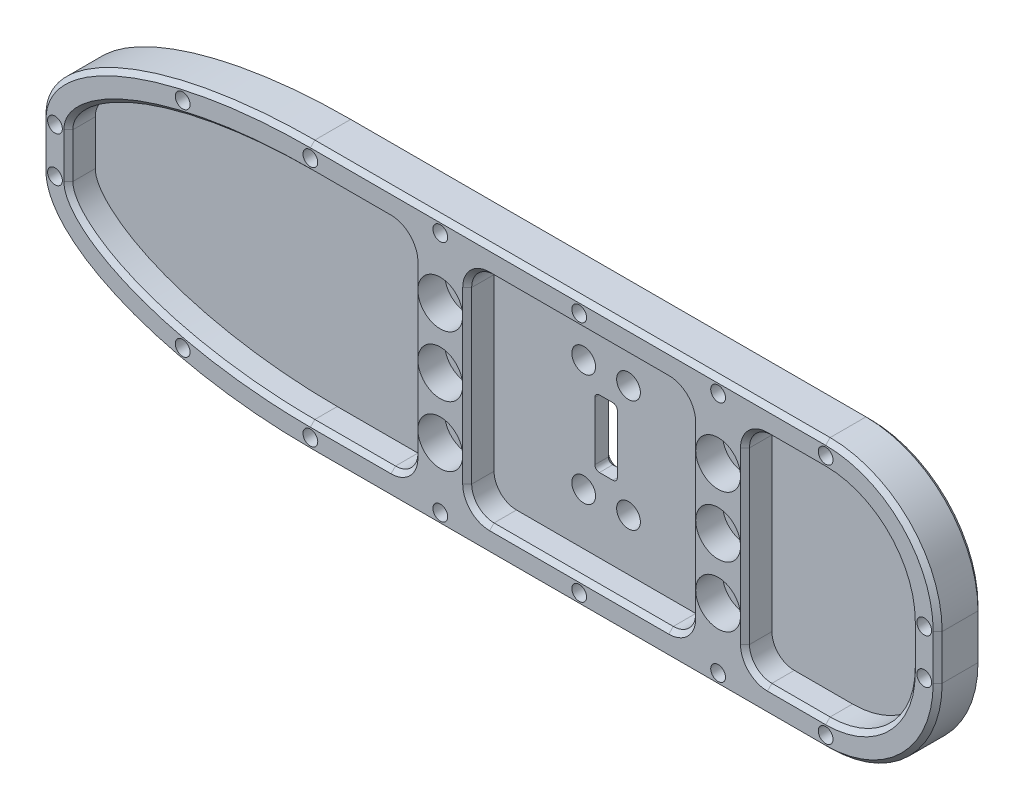
SolidWorks part; units mm, degrees
material "7075-T6 (SN)"
ref_plane "前视基准面" through (0, 0, 0) normal (0, 0, 1) x (1, 0, 0)
ref_plane "上视基准面" through (0, 0, 0) normal (0, 1, 0) x (1, 0, 0)
ref_plane "右视基准面" through (0, 0, 0) normal (1, 0, 0) x (0, 0, -1)
sketch "草图1" plane through (0, 0, 0) normal (0, 0, 1) x (1, 0, 0)
  line L0 (-20, 6.5) -> (-20, -6.5) construction
  line L1 (-19.4142, 6.5) -> (-20.5858, 6.5) construction
  line L2 (-20.5858, -6.5) -> (-19.4142, -6.5) construction
  line L3 (-20, 30) -> (-20, -30) construction
  line L4 (-20, 0) -> (60, 0) construction
  line L5 (-20, 0) -> (-140, 0) construction
  line L6 (-140, 0) -> (-140, -30) construction
  line L7 (60, 0) -> (60, 30) construction
  line L8 (-45, -14.5) -> (-45, -16.5) construction
  line L9 (-140, -30) -> (60, -30)
  line L10 (-140, -30) -> (-140, 30)
  line L11 (-140, 30) -> (60, 30)
  line L12 (60, -30) -> (60, 30)
  line L13 (-45, -16.5) -> (-57, -16.5) construction
  line L14 (-47, -16.5) -> (-55, -16.5) construction
  line L15 (17, -14.5) -> (17, -16.5) construction
  line L16 (15, -16.5) -> (17, -14.5) construction
  line L17 (17, 14.5) -> (17, -14.5) construction
  line L18 (17, -16.5) -> (15, -16.5) construction
  line L20 (-45, -16.5) -> (-57, -16.5)
  line L21 (-45, -16.5) -> (-45, 16.5)
  line L22 (-45, 16.5) -> (-57, 16.5)
  line L23 (-57, -16.5) -> (-57, 16.5)
  line L24 (17, -16.5) -> (5, -16.5)
  line L25 (17, -16.5) -> (17, 16.5)
  line L26 (17, 16.5) -> (5, 16.5)
  line L27 (5, -16.5) -> (5, 16.5)
  line L28 (-22.5, 7.5) -> (-17.5, 7.5)
  line L29 (-22.5, 7.5) -> (-22.5, -7.5)
  line L30 (-22.5, -7.5) -> (-17.5, -7.5)
  line L31 (-17.5, 7.5) -> (-17.5, -7.5)
  line L32 (-22.5, 7.5) -> (-17.5, -7.5) construction
  line L33 (-22.5, -7.5) -> (-17.5, 7.5) construction
  point P10 (-20, 0)
extrude "凸台-拉伸1" add sketch "草图1" along normal blind 10
fillet "圆角1" radius 1 12 edges at (5, 16.5, 5) (5, -16.5, 5) (17, -16.5, 5) (17, 16.5, 5) (-22.5, 7.5, 5) (-22.5, -7.5, 5) (-17.5, -7.5, 5) (-17.5, 7.5, 5) (-57, -16.5, 5) (-45, -16.5, 5) (-45, 16.5, 5) (-57, 16.5, 5)
fillet "圆角2" radius 25 2 edges at (60, -30, 5) (60, 30, 5)
fillet "圆角3" radius 60 2 edges at (-140, -30, 5) (-140, 30, 5)
sketch "草图2" plane through (0, 0, 2) normal (0, 0, 1) x (1, 0, 0)
  line L0 (6, -16.5) -> (16, -16.5) construction
  line L1 (17, -15.5) -> (17, 15.5) construction
  line L2 (16, 16.5) -> (6, 16.5) construction
  line L3 (5, 15.5) -> (5, -15.5) construction
  line L4 (-45, -15.5) -> (-45, 15.5) construction
  line L5 (-56, -16.5) -> (-46, -16.5) construction
  line L6 (-57, 15.5) -> (-57, -15.5) construction
  line L7 (-46, 16.5) -> (-56, 16.5) construction
  line L8 (6, -16.5) -> (16, -16.5)
  line L9 (17, -15.5) -> (17, 15.5)
  line L10 (16, 16.5) -> (6, 16.5)
  line L11 (5, 15.5) -> (5, -15.5)
  line L12 (-45, -15.5) -> (-45, 15.5)
  line L13 (-56, -16.5) -> (-46, -16.5)
  line L14 (-57, 15.5) -> (-57, -15.5)
  line L15 (-46, 16.5) -> (-56, 16.5)
  arc A0 (16, -16.5) -> (17, -15.5) centre (16, -15.5) ccw construction
  arc A1 (17, 15.5) -> (16, 16.5) centre (16, 15.5) ccw construction
  arc A2 (6, 16.5) -> (5, 15.5) centre (6, 15.5) ccw construction
  arc A3 (-46, -16.5) -> (-45, -15.5) centre (-46, -15.5) ccw construction
  arc A4 (-57, -15.5) -> (-56, -16.5) centre (-56, -15.5) ccw construction
  arc A5 (-56, 16.5) -> (-57, 15.5) centre (-56, 15.5) ccw construction
  arc A6 (-45, 15.5) -> (-46, 16.5) centre (-46, 15.5) ccw construction
  arc A7 (16, -16.5) -> (17, -15.5) centre (16, -15.5) ccw
  arc A8 (17, 15.5) -> (16, 16.5) centre (16, 15.5) ccw
  arc A9 (6, 16.5) -> (5, 15.5) centre (6, 15.5) ccw
  arc A10 (-46, -16.5) -> (-45, -15.5) centre (-46, -15.5) ccw
  arc A11 (-57, -15.5) -> (-56, -16.5) centre (-56, -15.5) ccw
  arc A12 (-56, 16.5) -> (-57, 15.5) centre (-56, 15.5) ccw
  arc A13 (-45, 15.5) -> (-46, 16.5) centre (-46, 15.5) ccw
  arc A14 (5, -15.5) -> (6, -16.5) centre (6, -15.5) ccw construction
  arc A15 (5, -15.5) -> (6, -16.5) centre (6, -15.5) ccw
extrude "凸台-拉伸2" add sketch "草图2" along normal up to surface (8 mm away) up to face at (11, 0, 10)
sketch "草图3" plane through (0, 0, 10) normal (0, 0, 1) x (1, 0, 0)
  line L0 (-45, 24) -> (-45, -24)
  line L1 (-57, 24) -> (-57, -24)
  line L2 (17, 24) -> (17, -24)
  line L3 (5, 24) -> (5, -24)
  line L4 (-57, 24) -> (-80, 24)
  line L5 (-45, -24) -> (5, -24)
  line L6 (17, -24) -> (35, -24)
  line L7 (5, 24) -> (-45, 24)
  line L8 (11, 13.5) -> (11, -13.5) construction
  line L9 (5, 0) -> (17, 0) construction
  line L10 (-51, -13.5) -> (-51, 13.5) construction
  line L11 (-45, 0) -> (-57, 0) construction
  line L12 (-134, 5) -> (-134, -5)
  line L13 (-80, -24) -> (35, -24)
  line L14 (54, -5) -> (54, 5)
  line L15 (35, 24) -> (-80, 24)
  line L16 (-134, 5) -> (-134, -5)
  line L17 (-80, -24) -> (-57, -24)
  line L18 (54, -5) -> (54, 5)
  line L19 (35, 24) -> (17, 24)
  line L20 (11, 13.5) -> (11, -13.5) construction
  line L21 (5, 0) -> (17, 0) construction
  line L22 (-51, -13.5) -> (-51, 13.5) construction
  line L23 (-45, 0) -> (-57, 0) construction
  arc A6 (35, -24) -> (54, -5) centre (35, -5) ccw
  arc A7 (54, 5) -> (35, 24) centre (35, 5) ccw
  arc A8 (35, -24) -> (54, -5) centre (35, -5) ccw
  arc A9 (54, 5) -> (35, 24) centre (35, 5) ccw
  spline S6 degree 3 poles (4756.0393, 1030.7106) (198.0526, 126.1715) (-140.7078, 27.1267) (-133.8393, -6.2556) (-133.7451, -6.5606) (-133.3923, -7.4528) (-133.0755, -7.9996) (-132.5322, -8.7799) (-132.3384, -9.0338) (-131.9356, -9.5251) (-131.7265, -9.7624) (-131.0797, -10.4534) (-130.623, -10.8863) (-129.6715, -11.711) (-129.1766, -12.1027) (-128.1565, -12.8532) (-127.6333, -13.2105) (-126.0438, -14.2321) (-124.9533, -14.8516) (-122.7261, -15.9976) (-121.5891, -16.5239) (-119.278, -17.5022) (-118.1026, -17.9545) (-114.538, -19.2166) (-112.1371, -19.9264) (-107.2998, -21.1552) (-104.8628, -21.6707) (-99.9581, -22.5373) (-97.4905, -22.8885) (-92.5289, -23.4494) (-90.0346, -23.6574) (236.6094, -41.6102) (593.0658, 1124.1985) (755.533, -4814.3595) knots -1.654516 -1.654516 -1.654516 -1.654516 0.015625 0.015625 0.03125 0.03125 0.0625 0.0625 0.078125 0.078125 0.09375 0.09375 0.125 0.125 0.15625 0.15625 0.1875 0.1875 0.25 0.25 0.3125 0.3125 0.375 0.375 0.5 0.5 0.625 0.625 0.75 0.75 0.875 0.875 17.035108 17.035108 17.035108 17.035108 only from (-134, -5) to (-80, -24)
  spline S7 degree 3 poles (501.663, 4795.8892) (785.7927, -1434.1881) (265.311, 63.8012) (-97.4581, 22.8929) (-99.932, 22.5416) (-103.6298, 21.8888) (-104.8602, 21.65) (-107.3161, 21.1259) (-108.5407, 20.8406) (-112.187, 19.9126) (-114.588, 19.2002) (-118.1299, 17.9441) (-119.3003, 17.4933) (-121.6158, 16.512) (-122.7595, 15.9817) (-124.4353, 15.1174) (-124.9878, 14.8176) (-126.0788, 14.1912) (-126.6182, 13.864) (-128.2033, 12.8419) (-129.2168, 12.1066) (-130.6342, 10.8757) (-131.0893, 10.4438) (-131.9519, 9.5207) (-132.3575, 9.0316) (-133.078, 7.9954) (-133.3979, 7.4401) (-133.7446, 6.5616) (-133.8382, 6.2604) (-141.744, -32.1036) (315.149, -131.378) (4388.3188, 2104.2864) knots -17.899786 -17.899786 -17.899786 -17.899786 0.25 0.25 0.375 0.375 0.4375 0.4375 0.5 0.5 0.625 0.625 0.6875 0.6875 0.75 0.75 0.78125 0.78125 0.8125 0.8125 0.875 0.875 0.90625 0.90625 0.9375 0.9375 0.96875 0.96875 0.984375 0.984375 2.888005 2.888005 2.888005 2.888005 only from (-80, 24) to (-134, 5)
  spline S8 degree 3 poles (-134, -5) (-134, -5.3216) (-133.9666, -5.6368) (-133.8393, -6.2556) (-133.7451, -6.5606) (-133.3923, -7.4528) (-133.0755, -7.9996) (-132.5322, -8.7799) (-132.3384, -9.0338) (-131.9356, -9.5251) (-131.7265, -9.7624) (-131.0797, -10.4534) (-130.623, -10.8863) (-129.6715, -11.711) (-129.1766, -12.1027) (-128.1565, -12.8532) (-127.6333, -13.2105) (-126.0438, -14.2321) (-124.9533, -14.8516) (-122.7261, -15.9976) (-121.5891, -16.5239) (-119.278, -17.5022) (-118.1026, -17.9545) (-114.538, -19.2166) (-112.1371, -19.9264) (-107.2998, -21.1552) (-104.8628, -21.6707) (-99.9581, -22.5373) (-97.4905, -22.8885) (-92.5289, -23.4494) (-90.0346, -23.6574) (-85.0202, -23.933) (-82.511, -24) (-80, -24) knots 0 0 0 0 0.015625 0.015625 0.03125 0.03125 0.0625 0.0625 0.078125 0.078125 0.09375 0.09375 0.125 0.125 0.15625 0.15625 0.1875 0.1875 0.25 0.25 0.3125 0.3125 0.375 0.375 0.5 0.5 0.625 0.625 0.75 0.75 0.875 0.875 1 1 1 1
  spline S9 degree 3 poles (-80, 24) (-85.021, 24) (-90.0141, 23.7323) (-97.4581, 22.8929) (-99.932, 22.5416) (-103.6298, 21.8888) (-104.8602, 21.65) (-107.3161, 21.1259) (-108.5407, 20.8406) (-112.187, 19.9126) (-114.588, 19.2002) (-118.1299, 17.9441) (-119.3003, 17.4933) (-121.6158, 16.512) (-122.7595, 15.9817) (-124.4353, 15.1174) (-124.9878, 14.8176) (-126.0788, 14.1912) (-126.6182, 13.864) (-128.2033, 12.8419) (-129.2168, 12.1066) (-130.6342, 10.8757) (-131.0893, 10.4438) (-131.9519, 9.5207) (-132.3575, 9.0316) (-133.078, 7.9954) (-133.3979, 7.4401) (-133.7446, 6.5616) (-133.8382, 6.2604) (-133.9669, 5.6357) (-134, 5.3193) (-134, 5) knots 0 0 0 0 0.25 0.25 0.375 0.375 0.4375 0.4375 0.5 0.5 0.625 0.625 0.6875 0.6875 0.75 0.75 0.78125 0.78125 0.8125 0.8125 0.875 0.875 0.90625 0.90625 0.9375 0.9375 0.96875 0.96875 0.984375 0.984375 1 1 1 1
  point P3 (45.7284, 30.0076)
  point P9 (-51, 0)
  point P13 (-45, 0)
  point P14 (11, 0)
  point P18 (-57, 0)
  point P21 (17, 0)
  point P24 (5, 0)
  dimension "D1" = 6
extrude "切除-拉伸1" cut sketch "草图3" against normal blind 6
hole_wizard "打孔尺寸(%根据)内六角圆柱头螺钉的类型1" positions "草图4" profile "草图5" counterbore size "M5" standard "GB" end condition through all
sketch "草图4" plane through (0, 0, 10) normal (0, 0, 1) x (1, 0, 0)
  point P0 (11, 13.5)
  point P3 (11, 0)
  point P6 (11, -13.5)
  point P9 (-51, -13.5)
  point P12 (-51, 0)
  point P15 (-51, 13.5)
sketch "草图5" plane through (11, 13.5, 10) normal (1, 0, 0) x (0, -1, 0)
  line L0 (0, 0) -> (0, 10.2125)
  line L1 (0, 10.2125) -> (2.65, 10.2125)
  line L3 (2.65, 10.2125) -> (2.65, 6)
  line L4 (2.65, 6) -> (5, 6)
  line L5 (5, 6) -> (5, 0)
  line L7 (5, 0) -> (0, 0)
  line L11 (0, -6.35) -> (0, 107.95) construction
  dimension "通孔孔直径" = 5.3
  dimension "通孔孔深度" = 10.2125
  dimension "柱形沉头孔直径" = 10
  dimension "柱形沉头孔深度" = 6
fillet "圆角4" radius 5 8 edges at (-57, 24, 7) (-57, -24, 7) (-45, -24, 7) (-45, 24, 7) (5, -24, 7) (5, 24, 7) (17, 24, 7) (17, -24, 7)
sketch "草图6" plane through (0, 0, 10) normal (0, 0, 1) x (1, 0, 0)
  line L4 (-80, 27) -> (-80, -27) construction
  line L5 (-137, 0) -> (-80, 0) construction
  line L6 (-108.5, 23.9242) -> (-108.5, -23.9242) construction
  line L7 (-51, 27) -> (-51, -27) construction
  line L8 (-137, 5) -> (-137, -5)
  line L9 (-80, -27) -> (35, -27)
  line L10 (57, -5) -> (57, 5)
  line L11 (35, 27) -> (-80, 27)
  line L12 (-137, 5) -> (-137, -5)
  line L13 (-80, -27) -> (35, -27)
  line L14 (57, -5) -> (57, 5)
  line L15 (35, 27) -> (-80, 27)
  line L16 (11, 27) -> (11, -27) construction
  line L17 (-51, 0) -> (11, 0) construction
  line L18 (-20, 27) -> (-20, -27) construction
  circle A2 centre (-51, 0) radius 2.65 construction
  circle A3 centre (11, 0) radius 2.65 construction
  arc A4 (35, -27) -> (57, -5) centre (35, -5) ccw
  arc A5 (57, 5) -> (35, 27) centre (35, 5) ccw
  arc A6 (35, -27) -> (57, -5) centre (35, -5) ccw
  arc A7 (57, 5) -> (35, 27) centre (35, 5) ccw
  spline S4 degree 3 poles (2782.2306, 680.8949) (128.842, 125.5863) (-147.0775, 31.5162) (-136.6428, -7.3449) (-136.5338, -7.6695) (-136.279, -8.3079) (-136.1352, -8.6171) (-135.6629, -9.52) (-135.2941, -10.0892) (-134.6819, -10.9071) (-134.4672, -11.1745) (-134.0239, -11.6939) (-133.7954, -11.9458) (-132.6233, -13.1713) (-131.5927, -14.0453) (-129.9577, -15.2544) (-129.3959, -15.641) (-128.2549, -16.3796) (-127.6765, -16.7317) (-125.9211, -17.7438) (-124.7238, -18.3596) (-122.287, -19.4992) (-121.0475, -20.0229) (-118.5341, -20.9954) (-117.2602, -21.4441) (-114.6838, -22.2791) (-113.3859, -22.664) (-109.4766, -23.7321) (-106.8451, -24.3282) (-102.8661, -25.0782) (-101.5344, -25.3041) (-98.8614, -25.7114) (-97.5193, -25.8929) (205.734, -62.1468) (578.3357, 968.5126) (632.357, -2808.3144) knots -1.805421 -1.805421 -1.805421 -1.805421 0.03125 0.03125 0.046875 0.046875 0.0625 0.0625 0.09375 0.09375 0.109375 0.109375 0.125 0.125 0.1875 0.1875 0.21875 0.21875 0.25 0.25 0.3125 0.3125 0.375 0.375 0.4375 0.4375 0.5 0.5 0.625 0.625 0.6875 0.6875 0.75 0.75 14.803914 14.803914 14.803914 14.803914 only from (-137, -5) to (-80, -27)
  spline S5 degree 3 poles (608.4548, 2791.2011) (646.334, -1069.663) (220.7438, 63.8682) (-98.8246, 25.7375) (-101.4933, 25.336) (-105.4826, 24.5856) (-106.808, 24.3109) (-109.4368, 23.7111) (-110.742, 23.3856) (-114.6276, 22.3262) (-117.1797, 21.514) (-120.9271, 20.0719) (-122.1626, 19.5534) (-124.5992, 18.4214) (-125.8005, 17.8082) (-128.1585, 16.4583) (-129.3213, 15.7193) (-130.9745, 14.5051) (-131.5114, 14.0819) (-132.5503, 13.1895) (-133.0534, 12.7189) (-133.9994, 11.7349) (-134.4441, 11.2204) (-135.2628, 10.1351) (-135.637, 9.5644) (-136.2823, 8.3414) (-136.5426, 7.7082) (-136.8128, 6.7166) (-136.8829, 6.3774) (-145.3112, -55.3716) (594.7178, -178.7084) (2829.5936, -425.7435) knots -14.55071 -14.55071 -14.55071 -14.55071 0.25 0.25 0.375 0.375 0.4375 0.4375 0.5 0.5 0.625 0.625 0.6875 0.6875 0.75 0.75 0.8125 0.8125 0.84375 0.84375 0.875 0.875 0.90625 0.90625 0.9375 0.9375 0.96875 0.96875 0.984375 0.984375 3.782552 3.782552 3.782552 3.782552 only from (-80, 27) to (-137, 5)
  spline S6 degree 3 poles (-137, -5) (-137, -5.6898) (-136.9068, -6.3615) (-136.6428, -7.3449) (-136.5338, -7.6695) (-136.279, -8.3079) (-136.1352, -8.6171) (-135.6629, -9.52) (-135.2941, -10.0892) (-134.6819, -10.9071) (-134.4672, -11.1745) (-134.0239, -11.6939) (-133.7954, -11.9458) (-132.6233, -13.1713) (-131.5927, -14.0453) (-129.9577, -15.2544) (-129.3959, -15.641) (-128.2549, -16.3796) (-127.6765, -16.7317) (-125.9211, -17.7438) (-124.7238, -18.3596) (-122.287, -19.4992) (-121.0475, -20.0229) (-118.5341, -20.9954) (-117.2602, -21.4441) (-114.6838, -22.2791) (-113.3859, -22.664) (-109.4766, -23.7321) (-106.8451, -24.3282) (-102.8661, -25.0782) (-101.5344, -25.3041) (-98.8614, -25.7114) (-97.5193, -25.8929) (-90.8061, -26.6955) (-85.4131, -27) (-80, -27) knots 0 0 0 0 0.03125 0.03125 0.046875 0.046875 0.0625 0.0625 0.09375 0.09375 0.109375 0.109375 0.125 0.125 0.1875 0.1875 0.21875 0.21875 0.25 0.25 0.3125 0.3125 0.375 0.375 0.4375 0.4375 0.5 0.5 0.625 0.625 0.6875 0.6875 0.75 0.75 1 1 1 1
  spline S7 degree 3 poles (-80, 27) (-85.4119, 27) (-90.7956, 26.6955) (-98.8246, 25.7375) (-101.4933, 25.336) (-105.4826, 24.5856) (-106.808, 24.3109) (-109.4368, 23.7111) (-110.742, 23.3856) (-114.6276, 22.3262) (-117.1797, 21.514) (-120.9271, 20.0719) (-122.1626, 19.5534) (-124.5992, 18.4214) (-125.8005, 17.8082) (-128.1585, 16.4583) (-129.3213, 15.7193) (-130.9745, 14.5051) (-131.5114, 14.0819) (-132.5503, 13.1895) (-133.0534, 12.7189) (-133.9994, 11.7349) (-134.4441, 11.2204) (-135.2628, 10.1351) (-135.637, 9.5644) (-136.2823, 8.3414) (-136.5426, 7.7082) (-136.8128, 6.7166) (-136.8829, 6.3774) (-136.9765, 5.6916) (-137, 5.3468) (-137, 5) knots 0 0 0 0 0.25 0.25 0.375 0.375 0.4375 0.4375 0.5 0.5 0.625 0.625 0.6875 0.6875 0.75 0.75 0.8125 0.8125 0.84375 0.84375 0.875 0.875 0.90625 0.90625 0.9375 0.9375 0.96875 0.96875 0.984375 0.984375 1 1 1 1
  point P5 (-108.5, 0)
  point P9 (-51, 0)
  point P21 (11, 0)
  point P31 (-20, 0)
  dimension "D1" = 3
hole_wizard "M4 螺纹孔1" positions "草图8" profile "草图9" tap size "M4" standard "GB" end condition through all
sketch "草图8" plane through (0, 0, 10) normal (0, 0, 1) x (1, 0, 0)
  point P0 (-137, 5)
  point P3 (-137, -5)
  point P6 (-108.5, -23.9242)
  point P9 (-108.5, 23.9242)
  point P12 (-80, 27)
  point P15 (-80, -27)
  point P18 (-51, -27)
  point P21 (-51, 27)
  point P24 (-20, 27)
  point P27 (-20, -27)
  point P30 (11, -27)
  point P33 (11, 27)
  point P36 (35, 27)
  point P39 (57, 5)
  point P42 (57, -5)
  point P45 (35, -27)
sketch "草图9" plane through (-137, 5, 10) normal (1, 0, 0) x (0, -1, 0)
  line L0 (0, 0) -> (0, 10.2125)
  line L1 (0, 10.2125) -> (1.65, 10.2125)
  line L2 (1.65, 10.2125) -> (1.65, 0)
  line L5 (1.65, 0) -> (0, 0)
  line L11 (0, -6.35) -> (0, 107.95) construction
  dimension "通孔螺纹孔钻头直径" = 3.3
  dimension "通孔螺纹孔钻头深度" = 10.2125
cosmetic thread "孔螺蚊线1" parameters "D2"=4
cosmetic thread "孔螺蚊线2" parameters "D2"=4
cosmetic thread "孔螺蚊线3" parameters "D2"=4
cosmetic thread "孔螺蚊线4" parameters "D2"=4
cosmetic thread "孔螺蚊线5" parameters "D2"=4
cosmetic thread "孔螺蚊线6" parameters "D2"=4
cosmetic thread "孔螺蚊线7" parameters "D2"=4
cosmetic thread "孔螺蚊线8" parameters "D2"=4
cosmetic thread "孔螺蚊线9" parameters "D2"=4
cosmetic thread "孔螺蚊线10" parameters "D2"=4
cosmetic thread "孔螺蚊线11" parameters "D2"=4
cosmetic thread "孔螺蚊线12" parameters "D2"=4
cosmetic thread "孔螺蚊线13" parameters "D2"=4
cosmetic thread "孔螺蚊线14" parameters "D2"=4
cosmetic thread "孔螺蚊线15" parameters "D2"=4
cosmetic thread "孔螺蚊线16" parameters "D2"=4
chamfer "倒角1" distance 1 angle 45 16 edges at (11, 16.5, 0) (5.2929, 16.2071, 0) (16.7071, 16.2071, 0) (5, 0, 0) (17, 0, 0) (5.2929, -16.2071, 0) (16.7071, -16.2071, 0) (11, -16.5, 0) (-51, 16.5, 0) (-56.7071, 16.2071, 0) (-45.2929, 16.2071, 0) (-57, 0, 0) (-45, 0, 0) (-56.7071, -16.2071, 0) (-45.2929, -16.2071, 0) (-51, -16.5, 0)
chamfer "倒角2" distance 1 angle 45 8 edges at (-22.5, 0, 0) (-22.2071, -7.2071, 0) (-22.2071, 7.2071, 0) (-20, -7.5, 0) (-20, 7.5, 0) (-17.7929, -7.2071, 0) (-17.7929, 7.2071, 0) (-17.5, 0, 0)
chamfer "倒角3" distance 1 angle 45 40 edges at (52.6777, -22.6777, 0) (60, 0, 0) (52.6777, 22.6777, 0) (52.6777, -22.6777, 10) (60, 0, 10) (52.6777, 22.6777, 10) (28.5, -24, 10) (48.435, -18.435, 10) (18.4645, -22.5355, 10) (54, 0, 10) (17, 0, 10) (48.435, 18.435, 10) (18.4645, 22.5355, 10) (28.5, 24, 10) (-20, -24, 10) (3.5355, -22.5355, 10) (-43.5355, -22.5355, 10) (5, 0, 10) (-45, 0, 10) (3.5355, 22.5355, 10) (-43.5355, 22.5355, 10) (-20, 24, 10) (-58.4645, -22.5355, 10) (-57, 0, 10) (-58.4645, 22.5355, 10)
sketch "草图10" plane through (0, 0, 0) normal (0, 0, -1) x (-1, 0, 0)
  line L8 (62, 19) -> (62, -19)
  line L9 (80, 19) -> (62, 19)
  line L10 (129, -4.9576) -> (129, 4.9581)
  line L11 (62, -19) -> (80, -19)
  line L12 (62, 19) -> (62, -19)
  line L13 (80, 19) -> (62, 19)
  line L14 (129, -4.9576) -> (129, 4.9581)
  line L15 (62, -19) -> (80, -19)
  spline S4 degree 3 poles (-3735.683, -1014.249) (124.4511, -12.6691) (131.4253, 0.0295) (128.8891, 5.2126) (128.8559, 5.2737) (128.7515, 5.4537) (128.6757, 5.5693) (128.4375, 5.9085) (128.2634, 6.1249) (127.7168, 6.7477) (127.3222, 7.1281) (126.4973, 7.8476) (126.0669, 8.1866) (125.1791, 8.8335) (124.7213, 9.1416) (123.3336, 10.0224) (122.3834, 10.5552) (120.4468, 11.5423) (119.4602, 11.9961) (117.4586, 12.8422) (116.4434, 13.2342) (114.3899, 13.9678) (113.3501, 14.3105) (110.216, 15.2686) (108.1068, 15.8171) (103.8565, 16.7692) (101.7151, 17.1714) (97.4049, 17.8511) (95.2354, 18.1285) (-211.1327, 49.2518) (-590.0843, -1053.6287) (-573.8669, 3836.9878) knots -0.317011 -0.317011 -0.317011 -0.317011 0.003906 0.003906 0.007812 0.007812 0.015625 0.015625 0.03125 0.03125 0.0625 0.0625 0.09375 0.09375 0.125 0.125 0.1875 0.1875 0.25 0.25 0.3125 0.3125 0.375 0.375 0.5 0.5 0.625 0.625 0.75 0.75 18.271622 18.271622 18.271622 18.271622 only from (129, 4.9581) to (80, 19)
  spline S5 degree 3 poles (-505.3503, -3825.5156) (-668.7083, 1167.0576) (-226.9123, -50.8123) (95.2138, -18.131) (97.3724, -17.8555) (100.6011, -17.3474) (101.6758, -17.1621) (103.8218, -16.7569) (104.8941, -16.5365) (108.0931, -15.8207) (110.205, -15.2717) (113.3343, -14.3156) (114.3709, -13.9743) (116.429, -13.2397) (117.4518, -12.8451) (119.4672, -11.9933) (120.4604, -11.5361) (122.4093, -10.5413) (123.366, -10.0035) (124.75, -9.1225) (125.2033, -8.8162) (126.088, -8.1696) (126.5186, -7.8301) (127.338, -7.1132) (127.7286, -6.7356) (128.2662, -6.1209) (128.4376, -5.9082) (128.6753, -5.5698) (128.752, -5.4534) (128.8566, -5.2733) (128.8896, -5.2124) (131.4086, -0.0329) (123.7706, 10.2312) (-3426.5306, 1821.0546) knots -18.231273 -18.231273 -18.231273 -18.231273 0.25 0.25 0.375 0.375 0.4375 0.4375 0.5 0.5 0.625 0.625 0.6875 0.6875 0.75 0.75 0.8125 0.8125 0.875 0.875 0.90625 0.90625 0.9375 0.9375 0.96875 0.96875 0.984375 0.984375 0.992187 0.992187 0.996094 0.996094 1.316814 1.316814 1.316814 1.316814 only from (80, -19) to (129, -4.9576)
  spline S6 degree 3 poles (129, 4.9581) (128.9792, 5.0245) (128.9501, 5.0879) (128.8891, 5.2126) (128.8559, 5.2737) (128.7515, 5.4537) (128.6757, 5.5693) (128.4375, 5.9085) (128.2634, 6.1249) (127.7168, 6.7477) (127.3222, 7.1281) (126.4973, 7.8476) (126.0669, 8.1866) (125.1791, 8.8335) (124.7213, 9.1416) (123.3336, 10.0224) (122.3834, 10.5552) (120.4468, 11.5423) (119.4602, 11.9961) (117.4586, 12.8422) (116.4434, 13.2342) (114.3899, 13.9678) (113.3501, 14.3105) (110.216, 15.2686) (108.1068, 15.8171) (103.8565, 16.7692) (101.7151, 17.1714) (97.4049, 17.8511) (95.2354, 18.1285) (88.7249, 18.7899) (84.3694, 19) (80, 19) knots 0 0 0 0 0.003906 0.003906 0.007812 0.007812 0.015625 0.015625 0.03125 0.03125 0.0625 0.0625 0.09375 0.09375 0.125 0.125 0.1875 0.1875 0.25 0.25 0.3125 0.3125 0.375 0.375 0.5 0.5 0.625 0.625 0.75 0.75 1 1 1 1
  spline S7 degree 3 poles (80, -19) (84.371, -19) (88.7215, -18.7897) (95.2138, -18.131) (97.3724, -17.8555) (100.6011, -17.3474) (101.6758, -17.1621) (103.8218, -16.7569) (104.8941, -16.5365) (108.0931, -15.8207) (110.205, -15.2717) (113.3343, -14.3156) (114.3709, -13.9743) (116.429, -13.2397) (117.4518, -12.8451) (119.4672, -11.9933) (120.4604, -11.5361) (122.4093, -10.5413) (123.366, -10.0035) (124.75, -9.1225) (125.2033, -8.8162) (126.088, -8.1696) (126.5186, -7.8301) (127.338, -7.1132) (127.7286, -6.7356) (128.2662, -6.1209) (128.4376, -5.9082) (128.6753, -5.5698) (128.752, -5.4534) (128.8566, -5.2733) (128.8896, -5.2124) (128.9503, -5.0878) (128.9791, -5.0247) (129, -4.9576) knots 0 0 0 0 0.25 0.25 0.375 0.375 0.4375 0.4375 0.5 0.5 0.625 0.625 0.6875 0.6875 0.75 0.75 0.8125 0.8125 0.875 0.875 0.90625 0.90625 0.9375 0.9375 0.96875 0.96875 0.984375 0.984375 0.992187 0.992187 0.996094 0.996094 1 1 1 1
  dimension "D1" = 5
extrude "切除-拉伸2" cut sketch "草图10" against normal blind 2
fillet "圆角5" radius 5 4 edges at (-62, 19, 1) (-62, -19, 1)
sketch "草图12" plane through (0, 0, 0) normal (0, 0, -1) x (-1, 0, 0)
  line L8 (-22, 19) -> (-35, 19)
  line L9 (-22, -19) -> (-22, 19)
  line L10 (-35, -19) -> (-22, -19)
  line L11 (-49, 5) -> (-49, -5)
  line L12 (-22, 19) -> (-35, 19)
  line L13 (-22, -19) -> (-22, 19)
  line L14 (-35, -19) -> (-22, -19)
  line L15 (-49, 5) -> (-49, -5)
  arc A8 (-49, -5) -> (-35, -19) centre (-35, -5) ccw
  arc A9 (-35, 19) -> (-49, 5) centre (-35, 5) ccw
  arc A10 (-49, -5) -> (-35, -19) centre (-35, -5) ccw
  arc A11 (-35, 19) -> (-49, 5) centre (-35, 5) ccw
  dimension "D1" = 5
extrude "切除-拉伸4" cut sketch "草图12" against normal blind 2
fillet "圆角6" radius 5 2 edges at (22, 19, 1) (22, -19, 1)
chamfer "倒角4" distance 1 angle 45 18 edges at (-63.4645, -17.5355, 0) (-62, 0, 0) (-63.4645, 17.5355, 0) (49, 0, 0) (44.8995, -14.8995, 0) (44.8995, 14.8995, 0) (31, -19, 0) (31, 19, 0) (23.4645, -17.5355, 0) (23.4645, 17.5355, 0) (22, 0, 0)
sketch "草图13" plane through (0, 0, 4) normal (0, 0, 1) x (1, 0, 0)
  circle A0 centre (-25, 12.5) radius 2.65
  circle A1 centre (-15, 12.5) radius 2.65
  circle A2 centre (-15, -12.5) radius 2.65
  circle A3 centre (-25, -12.5) radius 2.65
extrude "切除-拉伸5" cut sketch "草图13" against normal through all
